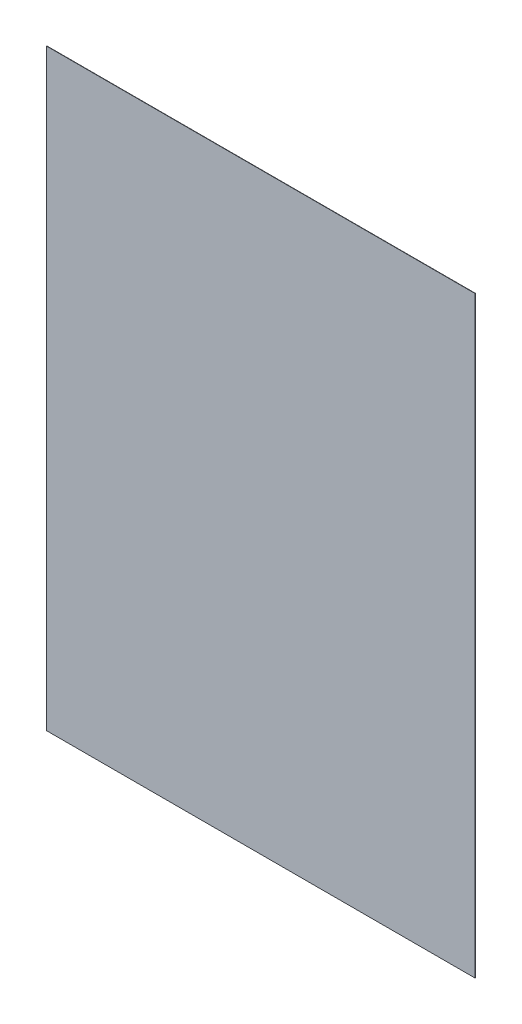
SolidWorks part; units mm, degrees
material "Papier falisty"
ref_plane "Płaszczyzna przednia" through (0, 0, 0) normal (0, 0, 1) x (1, 0, 0)
ref_plane "Płaszczyzna górna" through (0, 0, 0) normal (0, 1, 0) x (1, 0, 0)
ref_plane "Płaszczyzna prawa" through (0, 0, 0) normal (1, 0, 0) x (0, 0, -1)
sketch "Szkic1" plane through (0, 0, 0) normal (0, 0, 1) x (1, 0, 0)
  line L1 (0, 0) -> (1300, 0)
  line L2 (0, 0) -> (0, 1800)
  line L3 (0, 1800) -> (1300, 1800)
  line L4 (1300, 0) -> (1300, 1800)
  dimension "D1" = 1300
  dimension "D2" = 1800
base flange "Odgięcie bazowe1" sketch "Szkic1" thickness 1 reverse thickness direction no parameters "D1"=4
sketch "Linie zgięcia1" [suppressed] plane through (0, 0, 0) normal (0, 1, 0) x (1, 0, 0)
sketch "Ramka-graniczna1" [suppressed] plane through (0, 0, 0) normal (0, 1, 0) x (1, 0, 0)
sheet metal parameters "Arkusz blachy1" thickness 1 parameters "D1"=4
flat pattern "Rozłożony model1" [suppressed]
sketch "Linie zgięcia2" plane through (0, 0, 0) normal (0, 1, 0) x (1, 0, 0)
sketch3d "Ramka-graniczna2" [suppressed]
  line L0 (-1300, 1800, 0) -> (-1300, 0, 0) construction
  line L1 (0, 1800, 0) -> (0, 0, 0) construction
  line L2 (-1300, 1800, 0) -> (0, 1800, 0) construction
  line L3 (-1300, 0, 0) -> (0, 0, 0) construction
